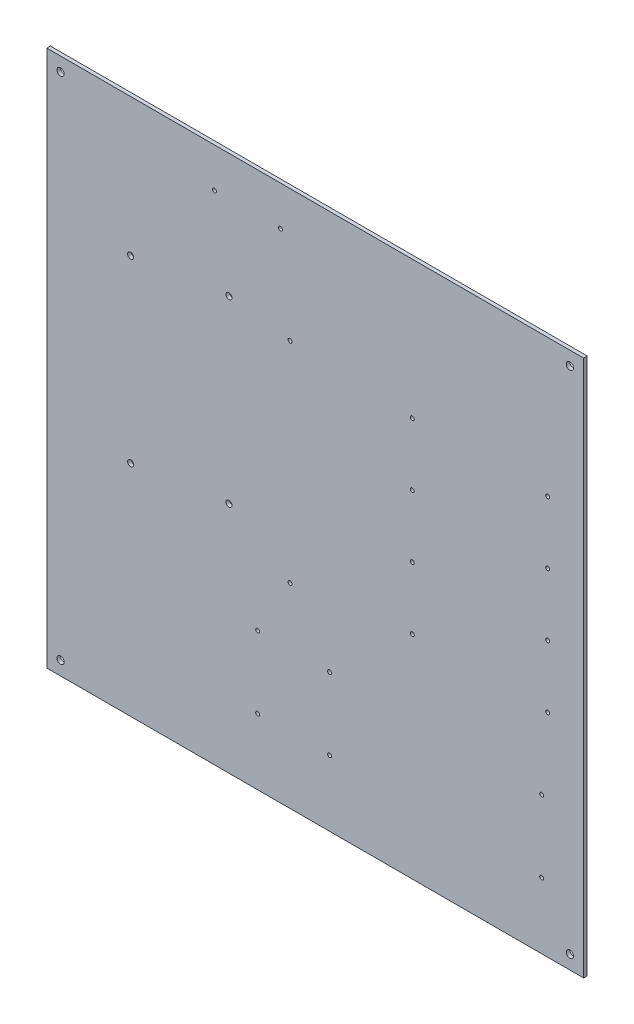
SolidWorks part; units mm, degrees
material "6061-T6 (SS)"
ref_plane "Piano frontale" through (0, 0, 0) normal (0, 0, 1) x (1, 0, 0)
ref_plane "Piano superiore" through (0, 0, 0) normal (0, 1, 0) x (1, 0, 0)
ref_plane "Piano destro" through (0, 0, 0) normal (1, 0, 0) x (0, 0, -1)
sketch "Schizzo1" plane through (0, 0, 0) normal (0, 0, 1) x (1, 0, 0)
  line L0 (0, 224) -> (448, 224) construction
  line L1 (0, 0) -> (448, 0)
  line L2 (0, 0) -> (0, 448)
  line L3 (0, 448) -> (448, 448)
  line L4 (448, 0) -> (448, 448)
  line L5 (224, 448) -> (224, 0) construction
  line L10 (0, 448) -> (0, 224) construction
  line L11 (0, 448) -> (0, 224) construction
  circle A0 centre (11.5, 436.5) radius 3
  circle A1 centre (436.5, 436.5) radius 3
  circle A2 centre (11.5, 11.5) radius 3
  circle A3 centre (436.5, 11.5) radius 3
  circle A4 centre (418, 177) radius 1.65
  circle A5 centre (305, 177) radius 1.65
  circle A6 centre (418, 229) radius 1.65
  circle A7 centre (305, 229) radius 1.65
  circle A8 centre (418, 281) radius 1.65
  circle A9 centre (305, 281) radius 1.65
  circle A10 centre (418, 333) radius 1.65
  circle A11 centre (305, 333) radius 1.65
  circle A12 centre (140, 415) radius 1.65
  circle A13 centre (195, 415) radius 1.65
  circle A14 centre (70, 333) radius 2.5
  circle A15 centre (70, 183) radius 2.5
  circle A16 centre (236, 55) radius 1.65
  circle A17 centre (236, 115) radius 1.65
  circle A18 centre (413, 115) radius 1.65
  circle A19 centre (413, 55) radius 1.65
  circle A20 centre (152, 344.7696) radius 2.5
  circle A21 centre (152, 194.7696) radius 2.5
  circle A22 centre (203, 338) radius 1.65
  circle A23 centre (203, 163) radius 1.65
  circle A24 centre (176, 115) radius 1.65
  circle A25 centre (176, 55) radius 1.65
  point P82 (253.9707, 256)
  point P89 (253.9707, 224)
  point P96 (253.9707, 192)
  point P103 (253.9707, 384)
  point P110 (253.9707, 352)
  point P117 (253.9707, 320)
  point P141 (253.9707, 288)
  point P148 (253.9707, 160)
  point P155 (253.9707, 128)
  point P162 (253.9707, 96)
  point P169 (253.9707, 64)
  point P179 (280.1758, 232.4048)
  point P193 (280.1085, 282.4047)
  point P207 (280.0413, 332.4047)
  dimension "D5" = 11.5
  dimension "D14" = 4
  dimension "D23" = 150
  dimension "D21" = 115
  dimension "D18" = 140
  dimension "D16" = 55
  dimension "D17" = 3.3
  dimension "D9" = 55
  dimension "D10" = 3.3
  dimension "D20" = 150
  dimension "D3" = 6
  dimension "D8" = 3.3
  dimension "D13" = 113
  dimension "D15" = 33
  dimension "D19" = 70
  dimension "D22" = 152
  dimension "D24" = 5
  dimension "D25" = 203
  dimension "D27" = 110
  dimension "D28" = 3.3
  dimension "D30" = 60
  dimension "D1" = 448
  dimension "D2" = 448
  dimension "D4" = 11.5
  dimension "D6" = 35
  dimension "D7" = 177
  dimension "D11" = 177
  dimension "D12" = 30
  dimension "D26" = 175
  dimension "D29" = 60
  dimension "D31" = 115
extrude "Estrusione-Estrusione1" add sketch "Schizzo1" against normal blind 3
